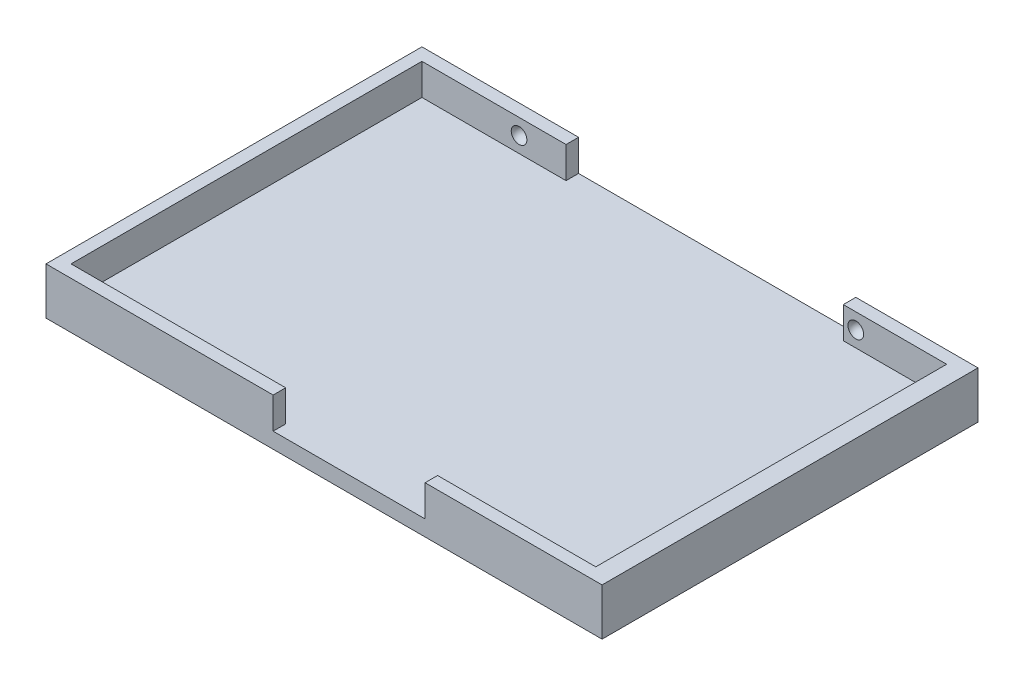
SolidWorks part; units mm, degrees
ref_plane "前视基准面" through (0, 0, 0) normal (0, 0, 1) x (1, 0, 0)
ref_plane "上视基准面" through (0, 0, 0) normal (0, 1, 0) x (1, 0, 0)
ref_plane "右视基准面" through (0, 0, 0) normal (1, 0, 0) x (0, 0, -1)
sketch "草图1" plane through (0, 0, 0) normal (0, 1, 0) x (1, 0, 0)
  line L1 (-17.75, 12) -> (17.75, 12)
  line L2 (-17.75, 12) -> (-17.75, -12)
  line L3 (-17.75, -12) -> (17.75, -12)
  line L4 (17.75, 12) -> (17.75, -12)
  line L5 (-17.75, 12) -> (17.75, -12) construction
  line L6 (-17.75, -12) -> (17.75, 12) construction
  point P0 (0, 0)
  dimension "D1" = 24
  dimension "D2" = 35.5
extrude "凸台-拉伸1" add sketch "草图1" along normal blind 3
sketch "草图2" plane through (0, 3, 0) normal (0, 1, 0) x (1, 0, 0)
  line L1 (-16.95, 11.2) -> (16.55, 11.2)
  line L2 (-16.95, 11.2) -> (-16.95, -11.2)
  line L3 (-16.95, -11.2) -> (16.55, -11.2)
  line L4 (16.55, 11.2) -> (16.55, -11.2)
  line L5 (-16.95, 11.2) -> (16.55, -11.2) construction
  line L6 (-16.95, -11.2) -> (16.55, 11.2) construction
  line L7 (-17.75, 12) -> (-17.75, -12) construction
  line L8 (17.75, -12) -> (17.75, 12) construction
  line L9 (17.75, 12) -> (-17.75, 12) construction
  line L10 (-17.75, -12) -> (17.75, -12) construction
  point P0 (0, 0)
  dimension "D1" = 0.8
  dimension "D2" = 0.8
  dimension "D3" = 1.2
  dimension "D4" = 0.8
extrude "切除-拉伸1" cut sketch "草图2" against normal blind 2
sketch "草图4" plane through (0, 3, 0) normal (0, 1, 0) x (1, 0, 0)
  line L0 (-16.95, -11.2) -> (16.55, -11.2) construction
  line L1 (-3.25, -11.2) -> (6.45, -11.2)
  line L2 (-3.25, -11.2) -> (-3.25, -12)
  line L3 (-3.25, -12) -> (6.45, -12)
  line L4 (6.45, -11.2) -> (6.45, -12)
  line L5 (-17.75, -12) -> (17.75, -12) construction
  line L6 (17.75, -12) -> (17.75, 12) construction
  line L7 (-17.75, 12) -> (-17.75, -12) construction
  dimension "D1" = 11.3
  dimension "D2" = 14.5
extrude "切除-拉伸2" cut sketch "草图4" against normal blind 2
sketch "草图5" plane through (0, 3, 0) normal (0, 1, 0) x (1, 0, 0)
  line L0 (17.75, 12) -> (-17.75, 12) construction
  line L1 (-7.75, 12) -> (9.95, 12)
  line L2 (-7.75, 12) -> (-7.75, 11.2)
  line L3 (-7.75, 11.2) -> (9.95, 11.2)
  line L4 (9.95, 12) -> (9.95, 11.2)
  line L5 (16.55, 11.2) -> (-16.95, 11.2) construction
  line L6 (17.75, -12) -> (17.75, 12) construction
  line L7 (-17.75, 12) -> (-17.75, -12) construction
  dimension "D1" = 7.8
  dimension "D2" = 10
extrude "切除-拉伸3" cut sketch "草图5" against normal blind 2
sketch "草图6" plane through (0, 0, 11.2) normal (0, 0, -1) x (-1, 0, 0)
  line L0 (-10.25, 2) -> (-11.25, 2)
  line L1 (-17.75, 3) -> (-17.75, 0) construction
  line L2 (-6.45, 3) -> (-16.55, 3) construction
  line L3 (10.25, 2) -> (11.25, 2)
  line L5 (17.75, 3) -> (17.75, 0) construction
  arc A0 (-11.25, 2) -> (-10.25, 2) centre (-10.75, 2) cw
  arc A1 (10.25, 2) -> (11.25, 2) centre (10.75, 2) cw
  dimension "D2" = 0.5
  dimension "D4" = 0.5
  dimension "D1" = 7
  dimension "D3" = 1
  dimension "D5" = 7
revolve "切除-旋转1" cut sketch "草图6" angle 360 about L0
sketch "草图7" plane through (0, 0, -11.2) normal (0, 0, 1) x (1, 0, 0)
  line L0 (-10.25, 2) -> (-11.25, 2)
  line L1 (10.25, 2) -> (11.25, 2)
  line L2 (-17.75, 3) -> (-17.75, 0) construction
  line L3 (-7.75, 3) -> (-16.95, 3) construction
  line L5 (17.75, 3) -> (17.75, 0) construction
  arc A0 (-11.25, 2) -> (-10.25, 2) centre (-10.75, 2) cw
  arc A1 (10.25, 2) -> (11.25, 2) centre (10.75, 2) cw
  dimension "D1" = 0.5
  dimension "D4" = 0.5
  dimension "D2" = 7
  dimension "D3" = 1
  dimension "D5" = 7
revolve "切除-旋转2" cut sketch "草图7" angle 360 about L0
